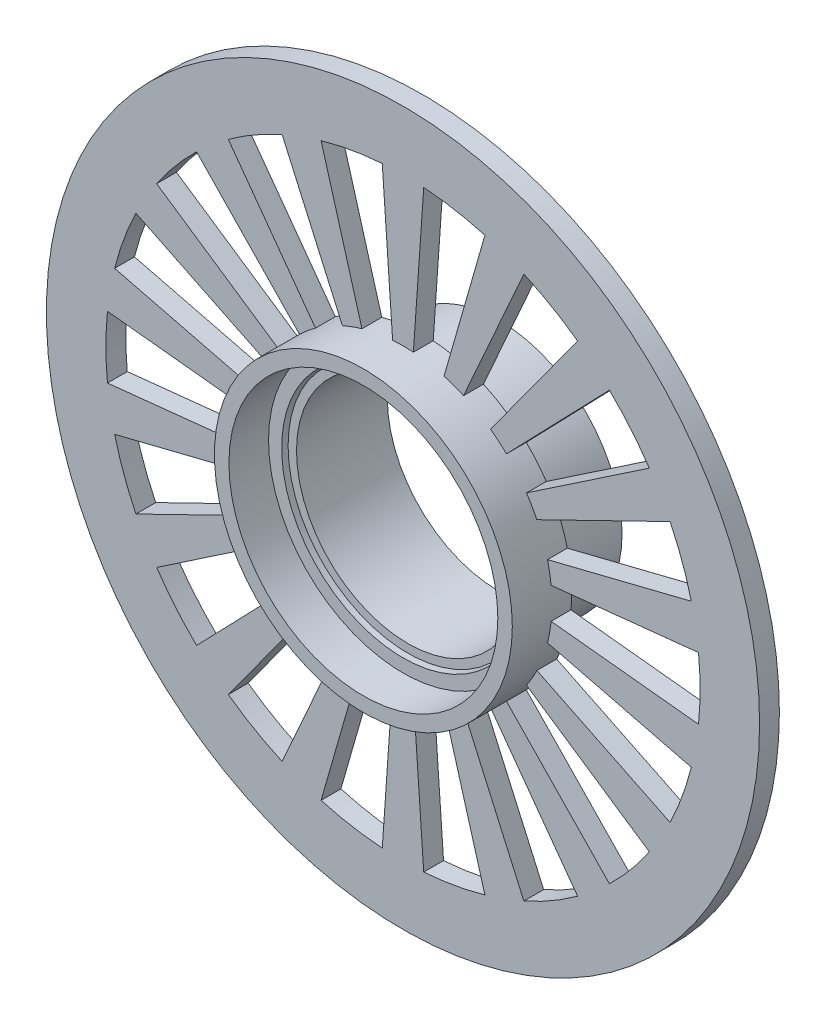
SolidWorks part; units mm, degrees
ref_plane "Front Plane" through (0, 0, 0) normal (0, 0, 1) x (1, 0, 0)
ref_plane "Top Plane" through (0, 0, 0) normal (0, 1, 0) x (1, 0, 0)
ref_plane "Right Plane" through (0, 0, 0) normal (1, 0, 0) x (0, 0, -1)
ref_plane "Plane1" through (0, 0, 19.4878) normal (0, 0, 1) x (1, 0, 0)
sketch "Sketch1" plane through (0, 0, 19.4878) normal (0, 0, 1) x (1, 0, 0)
  circle A0 centre (0, 0) radius 36
  circle A1 centre (0, 0) radius 12.5 construction
  circle A2 centre (0, 0) radius 11.25
  dimension "D1" = 72
  dimension "D2" = 25
  dimension "D3" = 22.5
extrude "Boss-Extrude1" add sketch "Sketch1" along normal blind 2
sketch "Sketch2" plane through (0, 0, 21.4878) normal (0, 0, 1) x (1, 0, 0)
  line L0 (0, 0) -> (0, 36) construction
  line L1 (0, 0) -> (12.3127, 33.8289) construction
  line L2 (0, 0) -> (2.5112, 35.9123) construction
  line L3 (0, 0) -> (9.9229, 34.6054) construction
  line L4 (2.5112, 35.9123) -> (0, 36) construction
  line L5 (9.9229, 34.6054) -> (12.3127, 33.8289) construction
  line L6 (2.0927, 29.9269) -> (1.0489, 15)
  line L7 (8.2691, 28.8379) -> (4.1447, 14.4541)
  line L8 (17.6336, 24.2705) -> (8.8383, 12.1649)
  line L9 (12.2021, 27.4064) -> (6.1159, 13.7366)
  line L10 (24.8711, 16.7758) -> (12.4659, 8.4084)
  line L11 (20.8398, 21.5802) -> (10.4453, 10.8164)
  line L12 (29.1089, 7.2577) -> (14.59, 3.6377)
  line L13 (26.9638, 13.1511) -> (13.5148, 6.5916)
  line L14 (29.8357, -3.1359) -> (14.9543, -1.5718)
  line L15 (29.8357, 3.1359) -> (14.9543, 1.5718)
  line L16 (26.9638, -13.1511) -> (13.5148, -6.5916)
  line L17 (29.1089, -7.2577) -> (14.59, -3.6377)
  line L18 (20.8398, -21.5802) -> (10.4453, -10.8164)
  line L19 (24.8711, -16.7758) -> (12.4659, -8.4084)
  line L20 (12.2021, -27.4064) -> (6.1159, -13.7366)
  line L21 (17.6336, -24.2705) -> (8.8383, -12.1649)
  line L22 (2.0927, -29.9269) -> (1.0489, -15)
  line L23 (8.2691, -28.8379) -> (4.1447, -14.4541)
  line L24 (-8.2691, -28.8379) -> (-4.1447, -14.4541)
  line L25 (-2.0927, -29.9269) -> (-1.0489, -15)
  line L26 (-17.6336, -24.2705) -> (-8.8383, -12.1649)
  line L27 (-12.2021, -27.4064) -> (-6.1159, -13.7366)
  line L28 (-24.8711, -16.7758) -> (-12.4659, -8.4084)
  line L29 (-20.8398, -21.5802) -> (-10.4453, -10.8164)
  line L30 (-29.1089, -7.2577) -> (-14.59, -3.6377)
  line L31 (-26.9638, -13.1511) -> (-13.5148, -6.5916)
  line L32 (-29.8357, 3.1359) -> (-14.9543, 1.5718)
  line L33 (-29.8357, -3.1359) -> (-14.9543, -1.5718)
  line L34 (-26.9638, 13.1511) -> (-13.5148, 6.5916)
  line L35 (-29.1089, 7.2577) -> (-14.59, 3.6377)
  line L36 (-20.8398, 21.5802) -> (-10.4453, 10.8164)
  line L37 (-24.8711, 16.7758) -> (-12.4659, 8.4084)
  line L38 (-12.2021, 27.4064) -> (-6.1159, 13.7366)
  line L39 (-17.6336, 24.2705) -> (-8.8383, 12.1649)
  line L40 (-2.0927, 29.9269) -> (-1.0489, 15)
  line L41 (-8.2691, 28.8379) -> (-4.1447, 14.4541)
  circle A0 centre (0, 0) radius 36 construction
  arc A1 (2.0927, 29.9269) -> (8.2691, 28.8379) centre (0, 0) cw
  arc A2 (1.0489, 15) -> (4.1447, 14.4541) centre (0, 0) cw
  circle A3 centre (0, 0) radius 11.25 construction
  arc A4 (6.1159, 13.7366) -> (8.8383, 12.1649) centre (0, 0) cw
  arc A5 (12.2021, 27.4064) -> (17.6336, 24.2705) centre (0, 0) cw
  arc A6 (10.4453, 10.8164) -> (12.4659, 8.4084) centre (0, 0) cw
  arc A7 (20.8398, 21.5802) -> (24.8711, 16.7758) centre (0, 0) cw
  arc A8 (13.5148, 6.5916) -> (14.59, 3.6377) centre (0, 0) cw
  arc A9 (26.9638, 13.1511) -> (29.1089, 7.2577) centre (0, 0) cw
  arc A10 (14.9543, 1.5718) -> (14.9543, -1.5718) centre (0, 0) cw
  arc A11 (29.8357, 3.1359) -> (29.8357, -3.1359) centre (0, 0) cw
  arc A12 (14.59, -3.6377) -> (13.5148, -6.5916) centre (0, 0) cw
  arc A13 (29.1089, -7.2577) -> (26.9638, -13.1511) centre (0, 0) cw
  arc A14 (12.4659, -8.4084) -> (10.4453, -10.8164) centre (0, 0) cw
  arc A15 (24.8711, -16.7758) -> (20.8398, -21.5802) centre (0, 0) cw
  arc A16 (8.8383, -12.1649) -> (6.1159, -13.7366) centre (0, 0) cw
  arc A17 (17.6336, -24.2705) -> (12.2021, -27.4064) centre (0, 0) cw
  arc A18 (4.1447, -14.4541) -> (1.0489, -15) centre (0, 0) cw
  arc A19 (8.2691, -28.8379) -> (2.0927, -29.9269) centre (0, 0) cw
  arc A20 (-1.0489, -15) -> (-4.1447, -14.4541) centre (0, 0) cw
  arc A21 (-2.0927, -29.9269) -> (-8.2691, -28.8379) centre (0, 0) cw
  arc A22 (-6.1159, -13.7366) -> (-8.8383, -12.1649) centre (0, 0) cw
  arc A23 (-12.2021, -27.4064) -> (-17.6336, -24.2705) centre (0, 0) cw
  arc A24 (-10.4453, -10.8164) -> (-12.4659, -8.4084) centre (0, 0) cw
  arc A25 (-20.8398, -21.5802) -> (-24.8711, -16.7758) centre (0, 0) cw
  arc A26 (-13.5148, -6.5916) -> (-14.59, -3.6377) centre (0, 0) cw
  arc A27 (-26.9638, -13.1511) -> (-29.1089, -7.2577) centre (0, 0) cw
  arc A28 (-14.9543, -1.5718) -> (-14.9543, 1.5718) centre (0, 0) cw
  arc A29 (-29.8357, -3.1359) -> (-29.8357, 3.1359) centre (0, 0) cw
  arc A30 (-14.59, 3.6377) -> (-13.5148, 6.5916) centre (0, 0) cw
  arc A31 (-29.1089, 7.2577) -> (-26.9638, 13.1511) centre (0, 0) cw
  arc A32 (-12.4659, 8.4084) -> (-10.4453, 10.8164) centre (0, 0) cw
  arc A33 (-24.8711, 16.7758) -> (-20.8398, 21.5802) centre (0, 0) cw
  arc A34 (-8.8383, 12.1649) -> (-6.1159, 13.7366) centre (0, 0) cw
  arc A35 (-17.6336, 24.2705) -> (-12.2021, 27.4064) centre (0, 0) cw
  arc A36 (-4.1447, 14.4541) -> (-1.0489, 15) centre (0, 0) cw
  arc A37 (-8.2691, 28.8379) -> (-2.0927, 29.9269) centre (0, 0) cw
  point P85 (0, 0)
  dimension "D1" = 20
  dimension "D2" = 4
  dimension "D3" = 6
  dimension "D4" = 15
  dimension "D5" = 18
extrude "Cut-Extrude1" cut sketch "Sketch2" against normal through all
sketch "Sketch3" plane through (0, 0, 19.4878) normal (0, 0, -1) x (-1, 0, 0)
  circle A0 centre (0, 0) radius 12.45
  circle A1 centre (0, 0) radius 11.25 construction
  circle A2 centre (0, 0) radius 11.25
  dimension "D1" = 24.9
extrude "Boss-Extrude2" add sketch "Sketch3" along normal blind 7.6662
split "Split1" bodies to split 103 resulting bodies 104 105 split by face at (36, 0, 19.4878)
sketch "Sketch4" plane through (0, 0, 21.4878) normal (0, 0, 1) x (1, 0, 0)
  circle A0 centre (0, 0) radius 12.25
  circle A1 centre (0, 0) radius 11.25 construction
  circle A2 centre (0, 0) radius 11.25
  dimension "D1" = 1
extrude "Cut-Extrude2" cut sketch "Sketch4" against normal up to surface (2 mm away) up to face at (-11.25, 0, 19.4878)
sketch "Sketch5" plane through (0, 0, 19.4878) normal (0, 0, 1) x (1, 0, 0)
  circle A0 centre (0, 0) radius 11.25 construction
  circle A1 centre (0, 0) radius 11.25
  circle A2 centre (0, 0) radius 12.25 construction
  circle A3 centre (0, 0) radius 12.25 construction
  circle A4 centre (0, 0) radius 12.1
  dimension "D1" = 0.15
extrude "Boss-Extrude3" add sketch "Sketch5" along normal offset from surface (1.5 mm away) 0.5 separate body up to face at (12.25, 0, 21.4878)
sketch "Sketch6" plane through (0, 0, 21.4878) normal (0, 0, 1) x (1, 0, 0)
  circle A0 centre (0, 0) radius 13.575
  circle A1 centre (0, 0) radius 15.0366
  dimension "D1" = 27.15
extrude "Boss-Extrude4" add sketch "Sketch6" along normal blind 4
ref_axis "Axis1" through (0, 0, 19.4878) along (0, 0, -1)
combine bodies "Combine1" operation type add bodies to combine 106 108
combine bodies "Combine2" operation type add bodies to combine 107 104
sketch "Sketch7" plane through (0, 0, 20.9878) normal (0, 0, 1) x (1, 0, 0)
  circle A0 centre (0, 0) radius 11.25
  circle A1 centre (0, 0) radius 12.25 construction
  circle A3 centre (0, 0) radius 12.25
  circle A4 centre (0, 0) radius 11.25 construction
ref_plane "Plane2" through (0, 0, 20.9878) normal (0, 0, 1) x (1, 0, 0)
